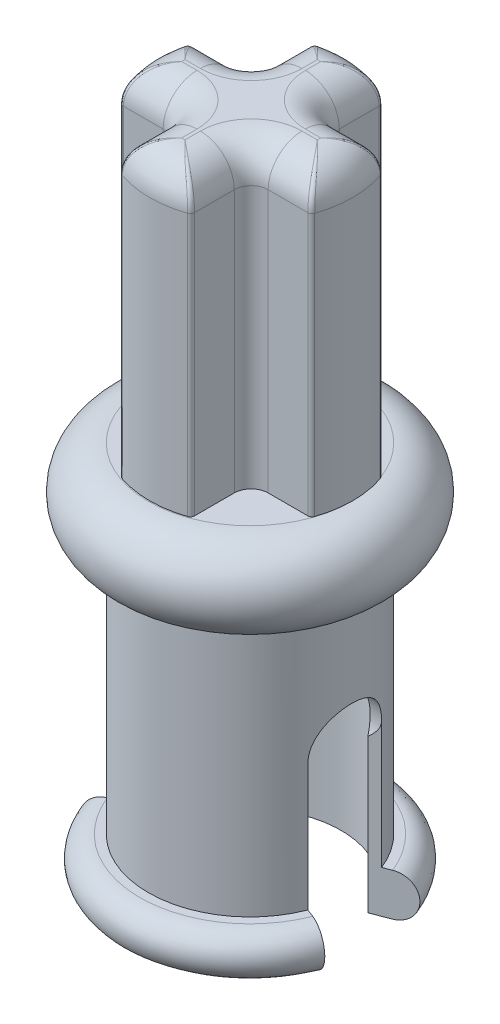
SolidWorks part; units mm, degrees
ref_plane "Front Plane" through (0, 0, 0) normal (0, 0, 1) x (1, 0, 0)
ref_plane "Top Plane" through (0, 0, 0) normal (0, 1, 0) x (1, 0, 0)
ref_plane "Right Plane" through (0, 0, 0) normal (1, 0, 0) x (0, 0, -1)
sketch "Sketch1" plane through (0, 0, 0) normal (0, 1, 0) x (1, 0, 0)
  circle A0 centre (0, 0) radius 3.4
  dimension "D1" = 6.8
extrude "Boss-Extrude1" add sketch "Sketch1" along normal mid plane 2
fillet "Fillet3" 2 edges at (0, 1, 3.4) (0, -1, 3.4) type full round first side face at (0, 1, 3.4) second side face at (0, -1, 3.4) middle face at (0, 1, 3.4)
sketch "Sketch2" plane through (0, 1, 0) normal (0, 1, 0) x (1, 0, 0)
  line L0 (-0.84, -1.2115) -> (-0.84, -2.1492)
  line L1 (-0.84, 2.2062) -> (-0.84, 1.2685)
  line L2 (0.84, 2.2062) -> (0.84, 1.2685)
  line L3 (-0.84, 2.2767) -> (0.84, -2.2197) construction
  line L4 (-0.84, -2.2197) -> (0.84, 2.2767) construction
  line L5 (-2.1777, 0.8685) -> (-1.24, 0.8685)
  line L6 (-2.1777, -0.8115) -> (-1.24, -0.8115)
  line L7 (-2.2482, 0.8685) -> (2.2482, -0.8115) construction
  line L8 (-2.2482, -0.8115) -> (2.2482, 0.8685) construction
  line L9 (1.24, 0.8685) -> (2.1777, 0.8685)
  line L10 (0.84, -1.2115) -> (0.84, -2.1492)
  line L11 (1.24, -0.8115) -> (2.1777, -0.8115)
  arc A0 (0.7722, 2.3009) -> (-0.7722, 2.3009) centre (0, 0.0285) ccw
  arc A1 (-2.2724, 0.8007) -> (-2.2724, -0.7437) centre (0, 0.0285) ccw
  arc A2 (2.2724, -0.7437) -> (2.2724, 0.8007) centre (0, 0.0285) ccw
  arc A3 (-0.7722, -2.2439) -> (0.7722, -2.2439) centre (0, 0.0285) ccw
  arc A4 (-2.1777, 0.8685) -> (-2.2724, 0.8007) centre (-2.1777, 0.7685) ccw
  arc A5 (-2.2724, -0.7437) -> (-2.1777, -0.8115) centre (-2.1777, -0.7115) ccw
  arc A6 (-0.84, -2.1492) -> (-0.7722, -2.2439) centre (-0.74, -2.1492) ccw
  arc A7 (0.7722, -2.2439) -> (0.84, -2.1492) centre (0.74, -2.1492) ccw
  arc A8 (2.1777, -0.8115) -> (2.2724, -0.7437) centre (2.1777, -0.7115) ccw
  arc A9 (2.1777, 0.8685) -> (2.2724, 0.8007) centre (2.1777, 0.7685) cw
  arc A10 (0.7722, 2.3009) -> (0.84, 2.2062) centre (0.74, 2.2062) cw
  arc A11 (-0.7722, 2.3009) -> (-0.84, 2.2062) centre (-0.74, 2.2062) ccw
  arc A12 (-0.84, -1.2115) -> (-1.24, -0.8115) centre (-1.24, -1.2115) ccw
  arc A13 (0.84, -1.2115) -> (1.24, -0.8115) centre (1.24, -1.2115) cw
  arc A14 (1.24, 0.8685) -> (0.84, 1.2685) centre (1.24, 1.2685) cw
  arc A15 (-1.24, 0.8685) -> (-0.84, 1.2685) centre (-1.24, 1.2685) ccw
extrude "Boss-Extrude2" add sketch "Sketch2" along normal blind 7
fillet "Fillet4" radius 0.8 24 edges at (-1.7089, 8, -0.8685) (-0.9572, 8, -0.9857) (-0.84, 8, -1.7374) (-0.8213, 8, -2.2644) (0, 8, -2.4285) (0.8213, 8, -2.2644) (0.84, 8, -1.7374) (0.9572, 8, -0.9857) (1.7089, 8, -0.8685) (2.2359, 8, -0.8498) (2.4, 8, -0.0285) (2.2359, 8, 0.7928) (1.7089, 8, 0.8115) (0.9572, 8, 0.9287) (0.84, 8, 1.6804) (0.8213, 8, 2.2074) (0, 8, 2.3715) (-0.8213, 8, 2.2074) (-0.84, 8, 1.6804) (-0.9572, 8, 0.9287) (-1.7089, 8, 0.8115) (-2.2359, 8, 0.7928) (-2.4, 8, -0.0285) (-2.2359, 8, -0.8498)
sketch "Sketch3" plane through (0, -1, 0) normal (0, -1, 0) x (1, 0, 0)
  circle A0 centre (0, 0) radius 2.4
  circle A1 centre (0, 0) radius 2.15
  dimension "D1" = 4.8
  dimension "D2" = 4.3
extrude "Boss-Extrude3" add sketch "Sketch3" along normal blind 6
sketch "Sketch4" plane through (0, -7, 0) normal (0, -1, 0) x (1, 0, 0)
  circle A0 centre (0, 0) radius 3.1
  circle A1 centre (0, 0) radius 2.15
  dimension "D1" = 6.2
extrude "Boss-Extrude4" add sketch "Sketch4" along normal blind 1
sketch "Sketch5" plane through (0, -8, 0) normal (0, -1, 0) x (1, 0, 0)
  line L0 (2.0038, 0.7793) -> (2.8892, 1.1236)
  line L1 (2.0038, -0.7793) -> (2.8892, -1.1236)
  line L2 (-2.0038, 0.7793) -> (-2.8892, 1.1236)
  line L3 (-2.0038, -0.7793) -> (-2.8892, -1.1236)
  circle A0 centre (0, 0) radius 3.1 construction
  arc A1 (-2.8892, -1.1236) -> (-2.8892, 1.1236) centre (0, 0) cw
  arc A2 (-2.0038, 0.7793) -> (-2.0038, -0.7793) centre (0, 0) ccw
  circle A3 centre (0, 0) radius 2.15 construction
  circle A4 centre (0, 0) radius 2.15 construction
  arc A5 (2.0038, 0.7793) -> (2.0038, -0.7793) centre (0, 0) cw
  arc A6 (2.8892, 1.1236) -> (2.8892, -1.1236) centre (0, 0) cw
  point P4 (0, 0)
  point P11 (0, 0)
  point P18 (0, 0)
  point P25 (0, 0)
  point P28 (0, 0)
  point P31 (0, 0)
  dimension "D1" = 0.95
extrude "Cut-Extrude1" cut sketch "Sketch5" against normal blind 4
sketch "Sketch6" plane through (0, 0, 0) normal (1, 0, 0) x (0, 0, -1)
  line L0 (-0.8699, -4) -> (0.8699, -4) construction
  circle A0 centre (0, -4) radius 0.8699
extrude "Cut-Extrude2" cut sketch "Sketch6" against normal mid plane 5
fillet "Fillet7" 2 edges at (0, -8, -3.1) (0, -7, -3.1) type full round first side face at (0, -8, -1.7882) second side face at (0, -7, -1.8734) middle face at (0, -7.5, -2.1118)
fillet "Fillet8" 2 edges at (0, -8, 3.1) (0, -7, 3.1) type full round first side face at (0, -8, 1.7882) second side face at (0, -7, 1.8734) middle face at (0, -7.5, 2.1118)
